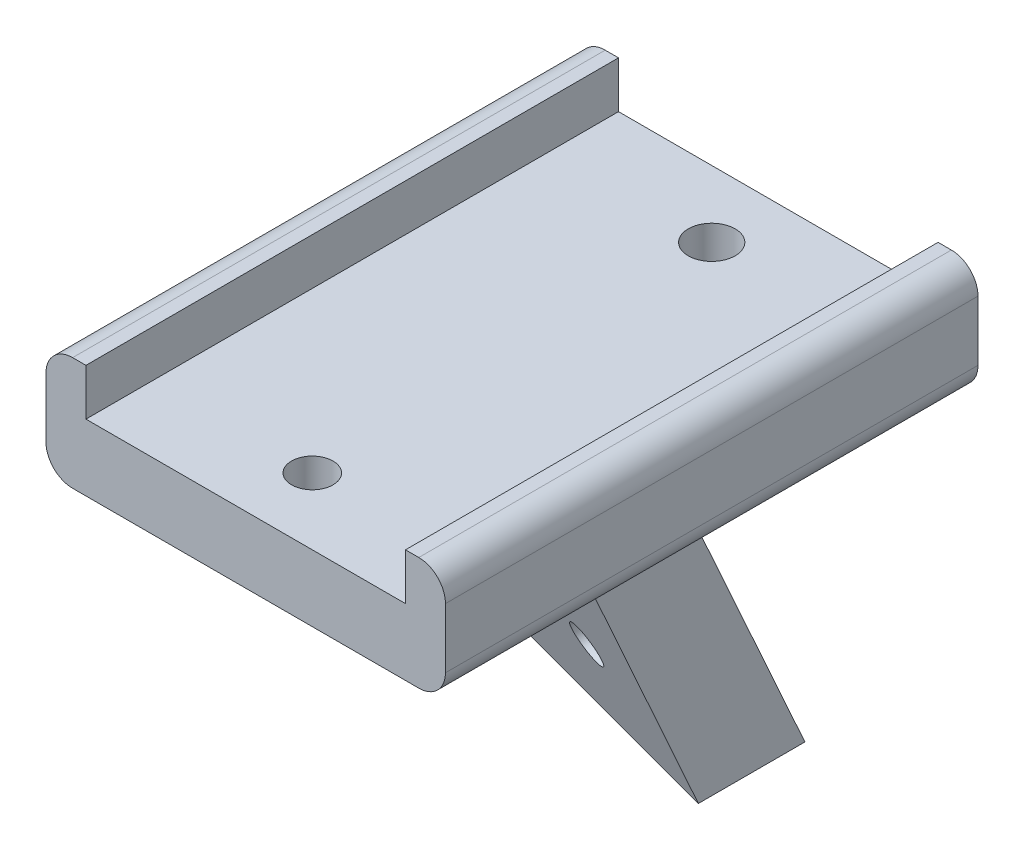
SolidWorks part; units mm, degrees
ref_plane "Front Plane" through (0, 0, 0) normal (0, 0, 1) x (1, 0, 0)
ref_plane "Top Plane" through (0, 0, 0) normal (0, 1, 0) x (1, 0, 0)
ref_plane "Right Plane" through (0, 0, 0) normal (1, 0, 0) x (0, 0, -1)
sketch "Sketch1" plane through (0, 0, 0) normal (0, 1, 0) x (1, 0, 0)
  line L1 (-11, -20) -> (11, -20)
  line L2 (-11, -20) -> (-11, 20)
  line L3 (-11, 20) -> (11, 20)
  line L4 (11, -20) -> (11, 20)
  line L5 (-11, -20) -> (11, 20) construction
  line L6 (-11, 20) -> (11, -20) construction
  circle A0 centre (0, 15) radius 1.7606
  circle A1 centre (0, -15) radius 1.5554
  point P0 (0, 0)
  dimension "D3" = 30
  dimension "D4" = 15
  dimension "D1" = 22
  dimension "D2" = 40
extrude "Boss-Extrude1" add sketch "Sketch1" along normal blind 5
sketch "Sketch2" plane through (0, 0, 0) normal (0, -1, 0) x (1, 0, 0)
  line L0 (-11, 0.1051) -> (11, 6)
  line L1 (-11, -20) -> (-11, 20) construction
  line L2 (11, 20) -> (11, -20) construction
  line L3 (11, 6) -> (11, -2)
  line L4 (11, -2) -> (-11, -7.8949)
  line L5 (-11, -7.8949) -> (-11, 0.1051)
  dimension "D1" = 8
  dimension "D2" = 14
  dimension "D3" = 105
sketch "Sketch4" plane through (0, 0, -20) normal (0, 0, -1) x (-1, 0, 0)
  line L0 (-11, 5) -> (-12, 5)
  line L1 (-12, 5) -> (-12, 8.5)
  line L2 (-12, 8.5) -> (-15, 8.5)
  line L3 (-15, 8.5) -> (-15, 0)
  line L4 (-15, 0) -> (-11, 0)
  line L5 (-11, 0) -> (-11, 5)
  line L6 (0, 0) -> (0, 5) construction
  line L7 (-11, 0) -> (11, 0) construction
  line L8 (-11, 5) -> (11, 5) construction
  line L9 (11, 0) -> (11, 5)
  line L10 (15, 0) -> (11, 0)
  line L11 (15, 8.5) -> (15, 0)
  line L12 (12, 8.5) -> (15, 8.5)
  line L13 (12, 5) -> (12, 8.5)
  line L14 (11, 5) -> (12, 5)
  dimension "D1" = 1
  dimension "D2" = 3.5
  dimension "D3" = 3
extrude "Boss-Extrude3" add sketch "Sketch4" against normal up to surface (40 mm away) up to face at (0, 2.5, 20)
fillet "Fillet1" radius 2 4 edges at (15, 0, 0) (-15, 0, 0) (-15, 8.5, 0) (15, 8.5, 0)
ref_plane "Plane1" through (0, -20, 0) normal (0, -1, 0) x (-1, 0, 0)
sketch "Sketch5" plane through (0, -20, 0) normal (0, -1, 0) x (-1, 0, 0)
  line L0 (-11, 3) -> (-11, 11)
  line L1 (-11, 11) -> (11, 16.8949)
  line L2 (11, 16.8949) -> (11, 8.8949)
  line L3 (11, 8.8949) -> (-11, 3)
  line L4 (-13, 20) -> (-13, -20) construction
  line L5 (13, -20) -> (13, 20) construction
  line L6 (13, -20) -> (-13, -20) construction
  dimension "D1" = 8
  dimension "D2" = 2
  dimension "D3" = 2
  dimension "D4" = 105
  dimension "D5" = 23
loft "Loft1" add profiles "Sketch2", "Sketch5" connector at (11, 0, -2) connector at (11, -20, -11)
ref_plane "Plane2" through (1.0403, 1.7471, -3.8825) normal (-0.2374, -0.3986, 0.8859) x (0.9714, -0.0974, 0.2165)
sketch "Sketch6" plane through (1.0403, 1.7471, -3.8825) normal (-0.2374, -0.3986, 0.8859) x (0.9714, -0.0974, 0.2165)
  line L0 (10.2527, -0.8207) -> (10.2527, -22.7524) construction
  line L1 (-12.3945, -3.2398) -> (-12.3945, -25.1715) construction
  line L2 (-12.3945, -3.2398) -> (10.2527, -0.8207) construction
  circle A0 centre (5.2527, -11.4117) radius 1.5
  circle A1 centre (-7.3945, -12.7626) radius 1.5
  point P6 (10.2527, -11.7866)
  dimension "D1" = 3
  dimension "D2" = 3
  dimension "D3" = 5
  dimension "D4" = 5
  dimension "D5" = 10
  dimension "D6" = 10
extrude "Cut-Extrude1" cut sketch "Sketch6" along normal up to surface (7.0869 mm away) up to face at (5.5, -5, 2.2763)
